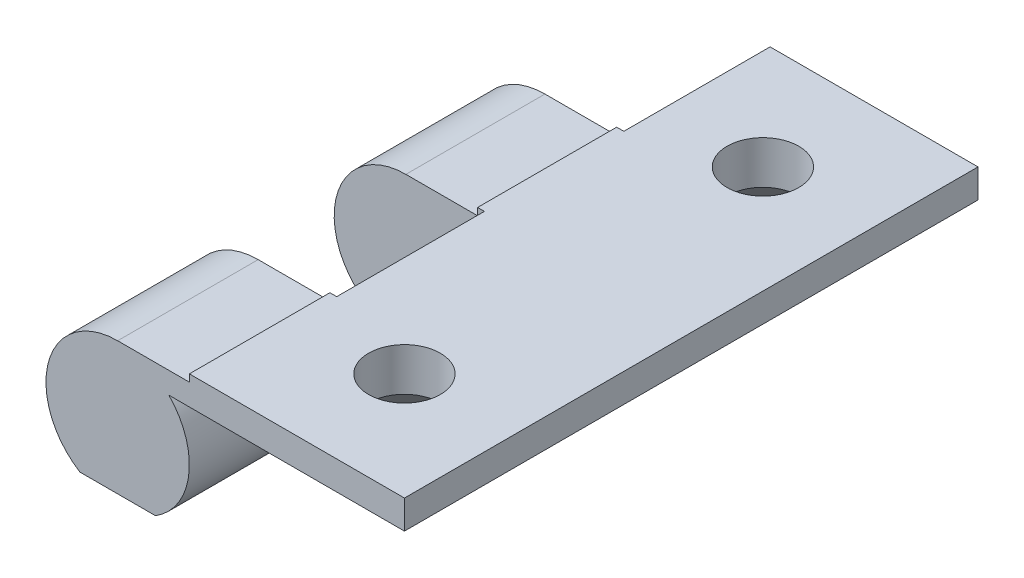
SolidWorks part; units mm, degrees
ref_plane "Ön Düzlem" through (0, 0, 0) normal (0, 0, 1) x (1, 0, 0)
ref_plane "Üst Düzlem" through (0, 0, 0) normal (0, 1, 0) x (1, 0, 0)
ref_plane "Sağ Düzlem" through (0, 0, 0) normal (1, 0, 0) x (0, 0, -1)
sketch "Çizim1" plane through (0, 0, 0) normal (0, 0, 1) x (1, 0, 0)
  line L0 (0, 5) -> (5, 5)
  line L1 (20, 5) -> (20, 0.5)
  line L2 (20, 0.5) -> (4.9749, 0.5)
  line L3 (20, 5) -> (20, 5.5)
  line L4 (20, 5.5) -> (5, 5.5)
  line L5 (5, 5.5) -> (5, 5)
  arc A0 (0, 5) -> (4.9749, 0.5) centre (0, 0) ccw
  circle A1 centre (0, 0) radius 3.5
  dimension "D1" = 10
  dimension "D7" = 7
  dimension "D2" = 20
  dimension "D3" = 4.5
  dimension "D4" = 0.5
  dimension "D5" = 15
  dimension "D6" = 5.5
extrude "Yükseklik-Ekstrüzyon1" add sketch "Çizim1" along normal blind 40
sketch "Çizim2" plane through (0, 0, 40) normal (0, 0, 1) x (1, 0, 0)
  line L0 (-6.3368, -4.25) -> (12.4224, -4.25)
  circle A1 centre (0, 0) radius 3.5 construction
  dimension "D1" = 4.25
extrude "Kes-Ekstrüzyon1" cut sketch "Çizim2" against normal through all and the other way through all flip side to cut
sketch "Çizim3" plane through (0, -4.25, 0) normal (0, -1, 0) x (1, 0, 0)
  line L1 (-5, 30) -> (5, 30)
  line L2 (-5, 30) -> (-5, 20)
  line L3 (-5, 20) -> (5, 20)
  line L4 (5, 30) -> (5, 20)
  line L6 (2.6339, 40) -> (-2.6339, 40) construction
  line L7 (5, 0) -> (-5, 0)
  line L8 (5, 0) -> (5, 10)
  line L9 (5, 10) -> (-5, 10)
  line L10 (-5, 0) -> (-5, 10)
  line L11 (20, 40) -> (20, 0) construction
  dimension "D1" = 10
  dimension "D2" = 10
  dimension "D3" = 10
  dimension "D4" = 10
  dimension "D5" = 10
  dimension "D6" = 15
  dimension "D7" = 15
  dimension "D8" = 10
extrude "Kes-Ekstrüzyon2" cut sketch "Çizim3" against normal through all
sketch "Çizim4" plane through (0, 0.5, 0) normal (0, -1, 0) x (1, 0, 0)
  line L1 (5, 0) -> (20, 0) construction
  line L2 (4.9749, 30) -> (5.4749, 30)
  line L3 (4.9749, 30) -> (4.9749, 20)
  line L4 (4.9749, 20) -> (5.4749, 20)
  line L5 (5.4749, 30) -> (5.4749, 20)
  line L6 (5, 10) -> (5.5, 10)
  line L7 (5, 10) -> (5, 0)
  line L8 (5, 0) -> (5.5, 0)
  line L11 (5.5, 10) -> (5.5, 0)
  dimension "D1" = 0.5
  dimension "D2" = 10
  dimension "D3" = 0.5
sketch "Çizim5" plane through (0, 0.5, 0) normal (0, -1, 0) x (1, 0, 0)
  line L2 (20, 20) -> (42.6437, 20) construction
  line L3 (5, 0) -> (20, 0) construction
  line L4 (20, 40) -> (20, 0) construction
  circle A0 centre (12.5, 7.5) radius 2.5
  circle A1 centre (12.5, 32.5) radius 2.5
  dimension "D1" = 7.5
  dimension "D2" = 7.5
  dimension "D3" = 5
extrude "Kes-Ekstrüzyon4" cut sketch "Çizim5" against normal through all
chamfer "Pah1" distance 3 angle 45 3 edges at (12.5, 0.5, 0) (20, 0.5, 20) (12.4875, 0.5, 40)
extrude "Kes-Ekstrüzyon5" cut sketch "Çizim4" against normal through all
chamfer "Pah2" distance 2 angle 45 2 edges at (12.5, 0.5, 5) (12.5, 0.5, 35)
sketch "Sketch1" plane through (0, 0, 40) normal (0, 0, 1) x (1, 0, 0)
  circle A0 centre (0, 0) radius 3.5 construction
  circle A1 centre (0, 0) radius 3.5
extrude "Boss-Extrude1" add sketch "Sketch1" against normal blind 10
sketch "Sketch2" plane through (0, 0, 20) normal (0, 0, 1) x (1, 0, 0)
  circle A0 centre (0, 0) radius 3.5 construction
  circle A1 centre (0, 0) radius 3.5
extrude "Boss-Extrude2" add sketch "Sketch2" against normal blind 10
sketch "Sketch3" plane through (0, 0, 30) normal (0, 0, -1) x (-1, 0, 0)
  line L6 (0, 5) -> (-5, 5)
  line L7 (-5, 5) -> (-5, 5.5)
  line L8 (-5, 5.5) -> (-5.4749, 5.5)
  line L9 (-5.4749, 5.5) -> (-5.4749, 0.5)
  line L10 (-5.4749, 0.5) -> (-4.9749, 0.5)
  line L11 (-2.6339, -4.25) -> (2.6339, -4.25)
  line L12 (0, 5) -> (-5, 5)
  line L13 (-5, 5) -> (-5, 5.5)
  line L14 (-5, 5.5) -> (-5.4749, 5.5)
  line L15 (-5.4749, 5.5) -> (-5.4749, 0.5)
  line L16 (-5.4749, 0.5) -> (-4.9749, 0.5)
  line L17 (-2.6339, -4.25) -> (2.6339, -4.25)
  arc A2 (2.6339, -4.25) -> (0, 5) centre (0, 0) ccw
  arc A3 (-4.9749, 0.5) -> (-2.6339, -4.25) centre (0, 0) ccw
  arc A4 (2.6339, -4.25) -> (0, 5) centre (0, 0) ccw
  arc A5 (-4.9749, 0.5) -> (-2.6339, -4.25) centre (0, 0) ccw
  dimension "D1" = 0
extrude "Cut-Extrude1" cut sketch "Sketch3" against normal blind 0.2
sketch "Sketch4" plane through (0, 0, 10) normal (0, 0, -1) x (-1, 0, 0)
  line L6 (-2.6339, -4.25) -> (2.6339, -4.25)
  line L7 (0, 5) -> (-5, 5)
  line L8 (-5, 5) -> (-5, 5.5)
  line L9 (-5, 5.5) -> (-5.5, 5.5)
  line L10 (-5.5, 5.5) -> (-5.5, 0.5)
  line L11 (-5.5, 0.5) -> (-4.9749, 0.5)
  line L12 (-2.6339, -4.25) -> (2.6339, -4.25)
  line L13 (0, 5) -> (-5, 5)
  line L14 (-5, 5) -> (-5, 5.5)
  line L15 (-5, 5.5) -> (-5.5, 5.5)
  line L16 (-5.5, 5.5) -> (-5.5, 0.5)
  line L17 (-5.5, 0.5) -> (-4.9749, 0.5)
  arc A2 (2.6339, -4.25) -> (0, 5) centre (0, 0) ccw
  arc A3 (-4.9749, 0.5) -> (-2.6339, -4.25) centre (0, 0) ccw
  arc A4 (2.6339, -4.25) -> (0, 5) centre (0, 0) ccw
  arc A5 (-4.9749, 0.5) -> (-2.6339, -4.25) centre (0, 0) ccw
  dimension "D1" = 0
extrude "Cut-Extrude2" cut sketch "Sketch4" against normal blind 0.2
sketch "Sketch5" plane through (0, 0, 20) normal (0, 0, 1) x (1, 0, 0)
  line L6 (4.9749, 0.5) -> (5.4749, 0.5)
  line L7 (5.4749, 0.5) -> (5.4749, 5.5)
  line L8 (5.4749, 5.5) -> (5, 5.5)
  line L9 (5, 5.5) -> (5, 5)
  line L10 (5, 5) -> (0, 5)
  line L11 (-2.6339, -4.25) -> (2.6339, -4.25)
  line L12 (4.9749, 0.5) -> (5.4749, 0.5)
  line L13 (5.4749, 0.5) -> (5.4749, 5.5)
  line L14 (5.4749, 5.5) -> (5, 5.5)
  line L15 (5, 5.5) -> (5, 5)
  line L16 (5, 5) -> (0, 5)
  line L17 (-2.6339, -4.25) -> (2.6339, -4.25)
  arc A2 (2.6339, -4.25) -> (4.9749, 0.5) centre (0, 0) ccw
  arc A3 (0, 5) -> (-2.6339, -4.25) centre (0, 0) ccw
  arc A4 (2.6339, -4.25) -> (4.9749, 0.5) centre (0, 0) ccw
  arc A5 (0, 5) -> (-2.6339, -4.25) centre (0, 0) ccw
  dimension "D1" = 0
extrude "Cut-Extrude3" cut sketch "Sketch5" against normal blind 0.1
ref_plane "Plane1" through (0, 0.375, 0) normal (0, -1, 0) x (-1, 0, 0)
sketch "Sketch6" plane through (0, 0.375, 0) normal (0, -1, 0) x (-1, 0, 0)
  line L0 (-2.6339, -30.2) -> (2.6339, -30.2) construction
  line L1 (0, -33.2) -> (0, -27.2)
  line L2 (0, -13.2) -> (0, -7.2)
  circle A0 centre (0, -30.2) radius 3
  circle A1 centre (0, -10.2) radius 3
revolve "Revolve1" add sketch "Sketch6" angle 360 about L2 region at (1.2732, 0.375, 10.2)
revolve "Cut-Revolve1" cut sketch "Sketch6<7>" angle 360 about L1 region at (1.2732, 0.375, 30.2)
sketch "Sketch6<7>" plane through (0, 0.375, 0) normal (0, -1, 0) x (-1, 0, 0) same geometry as "Sketch6"
